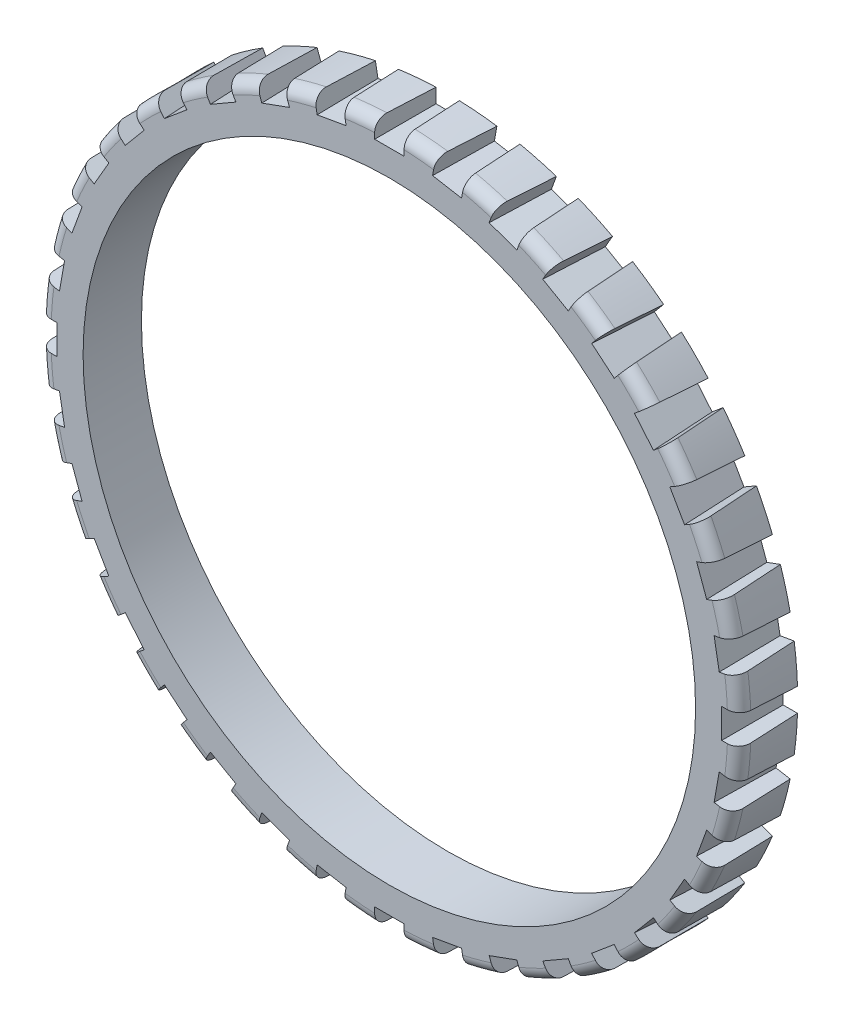
SolidWorks part; units mm, degrees
ref_plane "Front Plane" through (0, 0, 0) normal (0, 0, 1) x (1, 0, 0)
ref_plane "Top Plane" through (0, 0, 0) normal (0, 1, 0) x (1, 0, 0)
ref_plane "Right Plane" through (0, 0, 0) normal (1, 0, 0) x (0, 0, -1)
ref_plane "Plane2" through (0, 0, 12.7) normal (0, 0, 1) x (1, 0, 0)
sketch "Sketch3" plane through (0, 0, 12.7) normal (0, 0, 1) x (1, 0, 0)
  circle A0 centre (0, 0) radius 76.2
  circle A1 centre (0, 0) radius 66.675
extrude "Boss-Extrude2" add sketch "Sketch3" along normal blind 12.7 separate body
fillet "Fillet2" radius 2.54 1 edges at (76.2, 0, 25.4)
sketch "Sketch5" plane through (0, 0, 12.7) normal (0, 0, 1) x (1, 0, 0)
  line L3 (10.7232, 75.4417) -> (10.1792, 72.3567)
  line L4 (15.1821, 71.4745) -> (15.726, 74.5596)
  line L5 (10.1792, 72.3567) -> (15.1821, 71.4745)
  arc A0 (15.726, 74.5596) -> (10.7232, 75.4417) centre (0, 0) ccw
extrude "Cut-Extrude4" cut sketch "Sketch5" along normal blind 18.034 draft 3 draft outward yes
ref_axis "Axis1" through (0, 0, 22.86) along (0, 0, -1)
pattern_circular "CirPattern1" count 36 over 360 about axis through (0, 0, 22.86) along (0, 0, -1) of "Cut-Extrude4"
